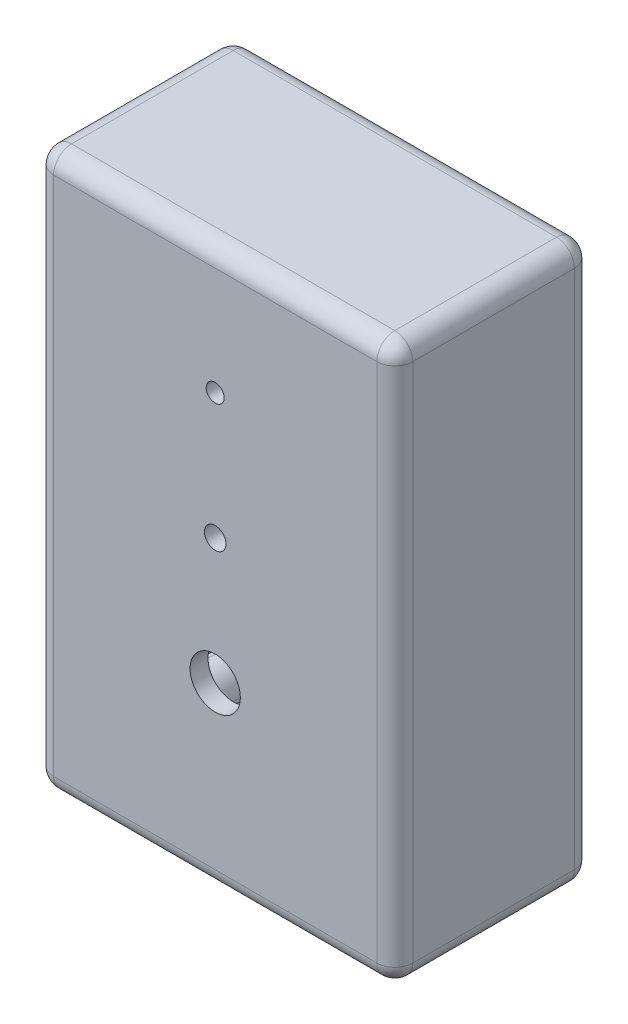
SolidWorks part; units mm, degrees
ref_plane "Front Plane" through (0, 0, 0) normal (0, 0, 1) x (1, 0, 0)
ref_plane "Top Plane" through (0, 0, 0) normal (0, 1, 0) x (1, 0, 0)
ref_plane "Right Plane" through (0, 0, 0) normal (1, 0, 0) x (0, 0, -1)
sketch "Sketch6" plane through (0, 0, 0) normal (0, 0, 1) x (1, 0, 0)
  line L1 (-50, -77.5) -> (50, -77.5)
  line L2 (-50, -77.5) -> (-50, 77.5)
  line L3 (-50, 77.5) -> (50, 77.5)
  line L4 (50, -77.5) -> (50, 77.5)
  line L5 (-50, -77.5) -> (50, 77.5) construction
  line L6 (-50, 77.5) -> (50, -77.5) construction
  point P0 (0, 0)
  dimension "D1" = 100
  dimension "D2" = 155
extrude "Boss-Extrude5" add sketch "Sketch6" along normal blind 55
fillet "Fillet2" radius 5 12 edges at (0, -77.5, 55) (-50, 0, 55) (0, 77.5, 55) (50, 0, 55) (-50, -77.5, 27.5) (50, -77.5, 27.5) (-50, 77.5, 27.5) (50, 77.5, 27.5) (0, 77.5, 0) (-50, 0, 0) (0, -77.5, 0) (50, 0, 0)
shell "Shell3" thickness 5 removed face at (0, 0, 0)
sketch "Sketch7" plane through (0, 0, 50) normal (0, 0, -1) x (-1, 0, 0)
  line L0 (0, 0) -> (0, -72.5) construction
  line L1 (-45, 72.5) -> (-37, 72.5)
  line L2 (-45, 72.5) -> (-45, 64.5)
  line L3 (-45, 64.5) -> (-44, 64.5)
  line L4 (-37, 72.5) -> (-37, 71.5)
  line L5 (45, -72.5) -> (-45, -72.5) construction
  line L6 (0, 0) -> (50, 0) construction
  line L7 (50, 72.5) -> (50, -72.5) construction
  line L8 (45, 72.5) -> (37, 72.5)
  line L9 (45, 72.5) -> (45, 64.5)
  line L10 (45, 64.5) -> (44, 64.5)
  line L11 (37, 72.5) -> (37, 71.5)
  line L12 (-45, -64.5) -> (-44, -64.5)
  line L13 (-37, -72.5) -> (-37, -71.5)
  line L14 (-45, -72.5) -> (-37, -72.5)
  line L15 (-45, -72.5) -> (-45, -64.5)
  line L16 (45, -72.5) -> (45, -64.5)
  line L17 (45, -64.5) -> (44, -64.5)
  line L18 (37, -72.5) -> (37, -71.5)
  line L19 (45, -72.5) -> (37, -72.5)
  arc A1 (44, 64.5) -> (37, 71.5) centre (44, 71.5) cw
  arc A2 (-37, 71.5) -> (-44, 64.5) centre (-44, 71.5) cw
  arc A3 (-37, -71.5) -> (-44, -64.5) centre (-44, -71.5) ccw
  arc A4 (44, -64.5) -> (37, -71.5) centre (44, -71.5) ccw
  circle A5 centre (-42, 69.5) radius 2.1 construction
  point P19 (37, 64.5)
  point P22 (-37, 64.5)
  dimension "D3" = 7
  dimension "D4" = 4.2
  dimension "D1" = 8
  dimension "D2" = 8
  dimension "D5" = 3
  dimension "D6" = 3
extrude "Boss-Extrude6" add sketch "Sketch7" along normal blind 45
sketch "Sketch8" plane through (0, 0, 5) normal (0, 0, -1) x (-1, 0, 0)
  line L0 (-37, 72.5) -> (-45, 72.5) construction
  line L1 (-45, 72.5) -> (-45, 64.5) construction
  line L2 (0, 0) -> (0, -72.5) construction
  line L3 (37, -72.5) -> (-37, -72.5) construction
  line L4 (0, 0) -> (45, 0) construction
  line L5 (45, 64.5) -> (45, -64.5) construction
  circle A0 centre (-42, 69.5) radius 2.1
  circle A1 centre (42, 69.5) radius 2.1
  circle A2 centre (42, -69.5) radius 2.1
  circle A3 centre (-42, -69.5) radius 2.1
  dimension "D1" = 4.2
  dimension "D2" = 3
  dimension "D3" = 3
extrude "Cut-Extrude1" cut sketch "Sketch8" against normal blind 6.5
sketch "Sketch9" plane through (0, 0, 55) normal (0, 0, 1) x (1, 0, 0)
  line L0 (0, 72.5) -> (0, -72.5) construction
  line L1 (45, 72.5) -> (-45, 72.5) construction
  line L2 (-45, -72.5) -> (45, -72.5) construction
  circle A0 centre (0, 42.5) radius 2.5
  circle A1 centre (0, 7.5) radius 3
  circle A2 centre (0, -27.5) radius 7
  dimension "D1" = 5
  dimension "D2" = 6
  dimension "D3" = 14
  dimension "D4" = 30
  dimension "D5" = 65
  dimension "D6" = 100
extrude "Cut-Extrude2" cut sketch "Sketch9" against normal through all
sketch "Sketch10" plane through (0, -77.5, 0) normal (0, -1, 0) x (1, 0, 0)
  line L0 (0, 50) -> (0, 0) construction
  line L1 (45, 50) -> (-45, 50) construction
  line L2 (0, 50) -> (9, 50) construction
  line L3 (-3.5, 50) -> (3.5, 50)
  line L4 (5.5, 48) -> (5.5, 47.8)
  line L5 (3.5, 45.8) -> (-3.5, 45.8)
  line L6 (-5.5, 48) -> (-5.5, 47.8)
  arc A0 (5.5, 48) -> (3.5, 50) centre (3.5, 48) ccw
  arc A1 (5.5, 47.8) -> (3.5, 45.8) centre (3.5, 47.8) cw
  arc A2 (-5.5, 47.8) -> (-3.5, 45.8) centre (-3.5, 47.8) ccw
  arc A3 (-5.5, 48) -> (-3.5, 50) centre (-3.5, 48) cw
  point P11 (5.5, 50)
  point P14 (5.5, 45.8)
  point P16 (0, 45.8)
  dimension "D4" = 2
  dimension "D1" = 9
  dimension "D2" = 5.5
  dimension "D3" = 4.2
extrude "Cut-Extrude3" cut sketch "Sketch10" against normal up to next
sketch "Sketch13" plane through (0, -72.5, 0) normal (0, 1, 0) x (1, 0, 0)
  line L3 (-5.5, -48) -> (-5.5, -47.8) construction
  line L4 (-3.5, -45.8) -> (3.5, -45.8) construction
  line L5 (5.5, -47.8) -> (5.5, -48) construction
  line L6 (5.5, -47.8) -> (5.5, -48)
  line L7 (-3.5, -45.8) -> (3.5, -45.8)
  line L8 (-5.5, -48) -> (-5.5, -47.8)
  line L9 (-3.5, -50) -> (3.5, -50)
  line L10 (0, -50) -> (0, -48.8) construction
  line L11 (-5.333, -48.8) -> (-10.333, -48.8)
  line L12 (-10.333, -48.8) -> (-10.333, -50)
  line L13 (-3.5, -50) -> (-45, -50) construction
  line L14 (-10.333, -50) -> (-3.5, -50)
  line L15 (10.333, -50) -> (3.5, -50)
  line L16 (10.333, -48.8) -> (10.333, -50)
  line L17 (5.333, -48.8) -> (10.333, -48.8)
  arc A4 (-5.5, -48) -> (-3.5, -50) centre (-3.5, -48) ccw construction
  arc A5 (-3.5, -45.8) -> (-5.5, -47.8) centre (-3.5, -47.8) ccw construction
  arc A6 (5.5, -47.8) -> (3.5, -45.8) centre (3.5, -47.8) ccw construction
  arc A7 (3.5, -50) -> (5.5, -48) centre (3.5, -48) ccw construction
  arc A8 (5.333, -48.8) -> (5.5, -48) centre (3.5, -48) ccw
  arc A9 (5.5, -47.8) -> (3.5, -45.8) centre (3.5, -47.8) ccw
  arc A10 (-3.5, -45.8) -> (-5.5, -47.8) centre (-3.5, -47.8) ccw
  arc A11 (-5.5, -48) -> (-5.333, -48.8) centre (-3.5, -48) ccw
  dimension "D1" = 1.2
  dimension "D2" = 5
  dimension "D3" = 1.2
extrude "Cut-Extrude4" cut sketch "Sketch13" against normal blind 3
sketch "Sketch14" plane through (0, 0, 50) normal (0, 0, -1) x (-1, 0, 0)
  line L0 (0, -48.5) -> (0, -74.5) construction
  line L1 (45, -77.5) -> (-45, -77.5) construction
  line L2 (0, -74.5) -> (0, -48.5) construction
  line L4 (7.5, -46.6) -> (7.5, -46.5)
  line L5 (7.5, -46.5) -> (9.5, -46.5) construction
  line L6 (0, -74.5) -> (9.5, -74.5)
  line L7 (9.5, -46.5) -> (9.5, -74.5) construction
  line L10 (-7.5, -46.6) -> (7.5, -46.5)
  line L11 (-5.6, -48.5) -> (5.6, -48.5)
  arc A0 (7.5, -46.6) -> (5.6, -48.5) centre (5.6, -46.6) cw
  arc A1 (-7.5, -46.6) -> (-5.6, -48.5) centre (-5.6, -46.6) ccw
  point P13 (7.5, -48.5)
  point P15 (0, -46.5)
  dimension "D6" = 1.9
  dimension "D1" = 3
  dimension "D2" = 26
  dimension "D3" = 9.5
  dimension "D4" = 2
  dimension "D5" = 2
  dimension "D7" = 7.5
extrude "Boss-Extrude7" add sketch "Sketch14" along normal blind 3 contours L10 A1 L11 A0 L4 region at (-0.0677, -47.494, 50)
ref_plane "Plane1" through (0, 0, 0) normal (0, 0, -1) x (-1, 0, 0)
sketch "Sketch15" plane through (0, 0, 0) normal (0, 0, -1) x (-1, 0, 0)
  line L0 (-45.3, -72.8) -> (-45.3, 72.8)
  line L1 (-45, -72.5) -> (45, -72.5) construction
  line L2 (-45, -72.5) -> (-45, 72.5) construction
  line L3 (-45, 72.5) -> (45, 72.5) construction
  line L4 (45, -72.5) -> (45, 72.5) construction
  line L5 (-45, -72.5) -> (45, 72.5) construction
  line L6 (-45, 72.5) -> (45, -72.5) construction
  line L7 (-45.3, 72.8) -> (45.3, 72.8)
  line L8 (45.3, -72.8) -> (45.3, 72.8)
  line L9 (-45.3, -72.8) -> (45.3, -72.8)
  point P0 (0, 0)
  dimension "D1" = 0.3
extrude "Cut-Extrude5" cut sketch "Sketch15" against normal blind 5
